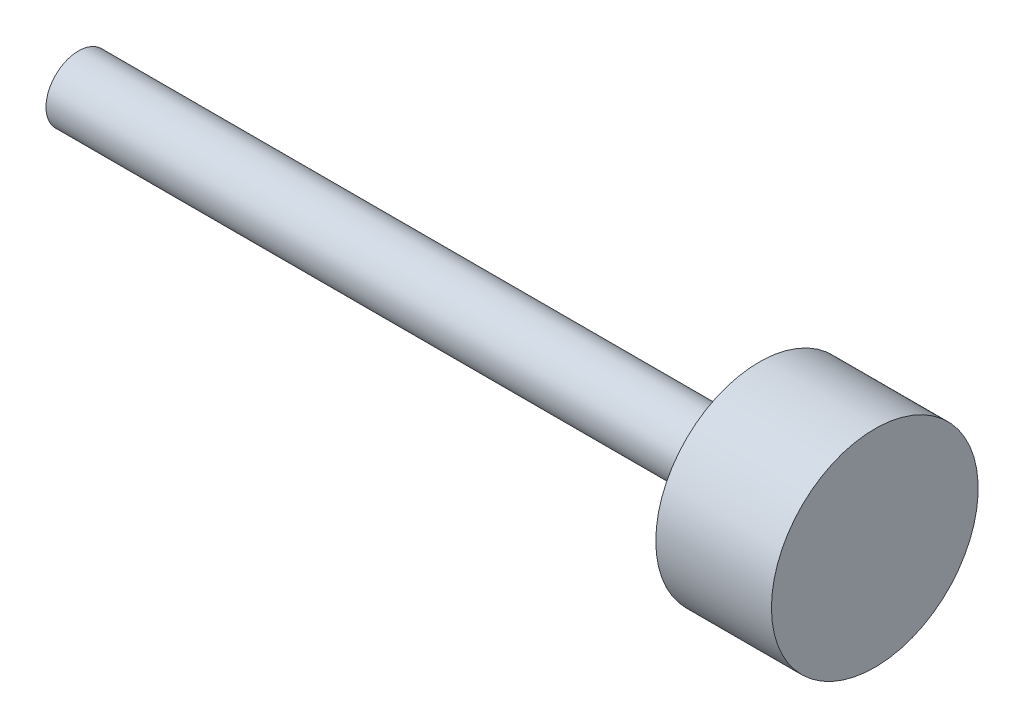
SolidWorks part; units mm, degrees
ref_plane "Front Plane" through (0, 0, 0) normal (0, 0, 1) x (1, 0, 0)
ref_plane "Top Plane" through (0, 0, 0) normal (0, 1, 0) x (1, 0, 0)
ref_plane "Right Plane" through (0, 0, 0) normal (1, 0, 0) x (0, 0, -1)
ref_plane "Plane1" through (-20.5232, 0, 0) normal (1, 0, 0) x (0, 0, -1)
ref_plane "Plane2" through (-20.5232, 0, 0) normal (1, 0, 0) x (0, 0, -1)
sketch "Sketch1" plane through (0, 0, 0) normal (0, 0, 1) x (1, 0, 0)
  line L0 (-22.225, 0) -> (-22.225, 8.001)
  line L1 (-22.225, 8.001) -> (145.3642, 8.001)
  line L2 (145.3642, 8.001) -> (145.3642, 25.4508)
  line L3 (145.3642, 25.4508) -> (173.8376, 25.4508)
  line L4 (173.8376, 25.4508) -> (173.8376, 0)
  line L5 (173.8376, 0) -> (-22.225, 0)
  line L6 (173.8376, 0) -> (-22.225, 0) construction
revolve "Revolve1" add sketch "Sketch1" angle 360 about L6 reverse direction yes
hole_wizard "Hole1" positions "Sketch3" profile "Sketch2" legacy
sketch "Sketch3" plane through (-22.225, 0, 0) normal (-1, 0, 0) x (0, 0, 1)
  point P0 (0, 0)
sketch "Sketch2" plane through (-22.225, 0, 0) normal (0, 1, 0) x (0, 0, 1)
  line L0 (0, 0) -> (0, 30.8737)
  line L1 (0, 30.8737) -> (4.8692, 28.0625)
  line L2 (4.8692, 28.0625) -> (4.8692, 0.6871)
  line L3 (4.8692, 0.6871) -> (5.5562, 0)
  line L4 (5.5562, 0) -> (0, 0)
  line L5 (0, -14.3089) -> (0, 102.4216) construction
  line L6 (0, 30.8737) -> (-4.8692, 28.0625) construction
  line L7 (-4.8692, 0.6871) -> (-5.5562, 0) construction
  dimension "Diameter" = 9.7384
  dimension "Depth" = 28.0625
  dimension "C-Sink Diameter" = 11.1125
  dimension "C-Sink Angle" = 90
  dimension "Drill Angle" = 120
cosmetic thread "Cosmetic Thread1" parameters "D1"=22.225, "D2"=11.1125
ref_plane "Plane3" through (-20.5232, 0, 0) normal (1, 0, 0) x (0, 0, -1)
ref_plane "i1 XY" through (0, 0, 0) normal (0, 0, 1) x (1, 0, 0)
ref_plane "i1 XZ" through (0, 8.001, 0) normal (0, -1, 0) x (-1, 0, 0)
ref_plane "i1 YZ" through (145.3642, 0, 0) normal (1, 0, 0) x (0, 0, -1)
ref_axis "i1 X" through (-80.9, 8.001, 0) along (1, 0, 0)
ref_axis "i1 Y" through (145.3642, -50, 0) along (0, 1, 0)
ref_axis "i1 Z" through (145.3642, 8.001, 80.9) along (0, 0, -1)
sketch3d "i1"
  point P0 (145.3642, 8.001, 0)
ref_plane "i2 XY" through (0, 0, 0) normal (0, 0, 1) x (1, 0, 0)
ref_plane "i2 XZ" through (0, -8.001, 0) normal (0, -1, 0) x (-1, 0, 0)
ref_plane "i2 YZ" through (145.3642, 0, 0) normal (1, 0, 0) x (0, 0, -1)
ref_axis "i2 X" through (-80.9, -8.001, 0) along (1, 0, 0)
ref_axis "i2 Y" through (145.3642, -50, 0) along (0, 1, 0)
ref_axis "i2 Z" through (145.3642, -8.001, 80.9) along (0, 0, -1)
sketch3d "i2"
  point P0 (145.3642, -8.001, 0)
ref_plane "to_rod_guide XY" through (-20.5232, 0, 0) normal (-1, 0, 0) x (0, 0, 1)
ref_plane "to_rod_guide XZ" through (0, 0, 0) normal (0, 1, 0) x (1, 0, 0)
ref_plane "to_rod_guide YZ" through (0, 0, 0) normal (0, 0, -1) x (-1, 0, 0)
ref_axis "to_rod_guide X" through (-20.5232, 0, 80.9) along (0, 0, -1)
ref_axis "to_rod_guide Y" through (-20.5232, 50, 0) along (0, -1, 0)
ref_axis "to_rod_guide Z" through (-80.9, 0, 0) along (1, 0, 0)
sketch3d "to_rod_guide"
  point P0 (-20.5232, 0, 0)
ref_plane "to_stud XY" through (-20.5232, 0, 0) normal (1, 0, 0) x (0, 0, -1)
ref_plane "to_stud XZ" through (0, 0, 0) normal (0, -1, 0) x (-1, 0, 0)
ref_plane "to_stud YZ" through (0, 0, 0) normal (0, 0, -1) x (-1, 0, 0)
ref_axis "to_stud X" through (-20.5232, 0, 80.9) along (0, 0, -1)
ref_axis "to_stud Y" through (-20.5232, -50, 0) along (0, 1, 0)
ref_axis "to_stud Z" through (80.9, 0, 0) along (-1, 0, 0)
sketch3d "to_stud"
  point P0 (-20.5232, 0, 0)
ref_plane "to_stud_old XY" through (-20.5232, 0, 0) normal (1, 0, 0) x (0, 0, -1)
ref_plane "to_stud_old XZ" through (0, 0, 0) normal (0, -1, 0) x (-1, 0, 0)
ref_plane "to_stud_old YZ" through (0, 0, 0) normal (0, 0, -1) x (-1, 0, 0)
ref_axis "to_stud_old X" through (-20.5232, 0, 80.9) along (0, 0, -1)
ref_axis "to_stud_old Y" through (-20.5232, -50, 0) along (0, 1, 0)
ref_axis "to_stud_old Z" through (80.9, 0, 0) along (-1, 0, 0)
sketch3d "to_stud_old"
  point P0 (-20.5232, 0, 0)
